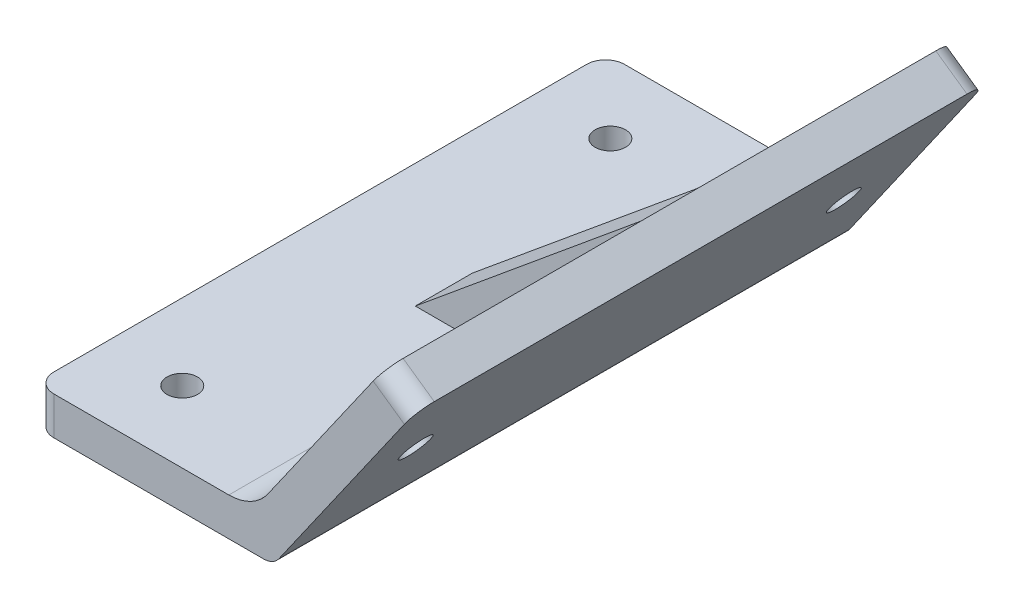
SolidWorks part; units mm, degrees
ref_plane "Front Plane" through (0, 0, 0) normal (0, 0, 1) x (1, 0, 0)
ref_plane "Top Plane" through (0, 0, 0) normal (0, 1, 0) x (1, 0, 0)
ref_plane "Right Plane" through (0, 0, 0) normal (1, 0, 0) x (0, 0, -1)
sketch "Sketch1" plane through (0, 0, 0) normal (0, 0, 1) x (1, 0, 0)
  line L0 (12.5411, -2) -> (27.4541, 19.298)
  line L1 (-12.5411, 2) -> (12.5411, 2)
  line L2 (-12.5411, 2) -> (-12.5411, -2)
  line L3 (-12.5411, -2) -> (12.5411, -2)
  line L4 (12.5411, 2) -> (12.5411, -2)
  line L5 (-12.5411, 2) -> (12.5411, -2) construction
  line L6 (-12.5411, -2) -> (12.5411, 2) construction
  line L7 (27.4541, 19.298) -> (24.1775, 21.5923)
  line L8 (24.1775, 21.5923) -> (10.4589, 2)
  point P0 (0, 0)
  dimension "D1" = 4
  dimension "D2" = 4
  dimension "D3" = 23
  dimension "D4" = 55
  dimension "D5" = 26
extrude "Boss-Extrude1" add sketch "Sketch1" against normal blind 30 and the other way blind 30 contours L7 L8 L1 L4 L0 | L4 L1 L2 L3 region at (18.9738, 10.6157, 0) region at (0, 0, 0)
sketch "Sketch2" plane through (0, 0, 0) normal (0, 0, 1) x (1, 0, 0)
  line L0 (24.1775, 21.5923) -> (0.4589, 2)
  line L1 (0.4589, 2) -> (10.4589, 2)
  line L6 (27.4541, 19.298) -> (24.1775, 21.5923)
  line L7 (24.1775, 21.5923) -> (10.4589, 2)
  line L8 (10.4589, 2) -> (-12.5411, 2)
  line L9 (-12.5411, 2) -> (-12.5411, -2)
  line L10 (-12.5411, -2) -> (12.5411, -2)
  line L11 (12.5411, -2) -> (27.4541, 19.298)
  line L12 (27.4541, 19.298) -> (24.1775, 21.5923)
  line L13 (24.1775, 21.5923) -> (10.4589, 2)
  line L14 (10.4589, 2) -> (-12.5411, 2)
  line L15 (-12.5411, 2) -> (-12.5411, -2)
  line L16 (-12.5411, -2) -> (12.5411, -2)
  line L17 (12.5411, -2) -> (27.4541, 19.298)
  dimension "D2" = 10
  dimension "D1" = 0
extrude "Boss-Extrude2" add sketch "Sketch2" along normal blind 3 and the other way blind 3 contours L13 L0 L1 region at (11.6984, 8.5308, 0)
sketch "Sketch3" plane through (9.3549, -6.5504, 0) normal (0.8192, -0.5736, 0) x (0, 0, -1)
  line L0 (-30, 18.555) -> (30, 18.555) construction
  line L1 (-30, 5.555) -> (-30, 31.555) construction
  line L2 (30, 5.555) -> (30, 31.555) construction
  line L3 (0, 31.555) -> (0, 5.555) construction
  line L4 (-30, 31.555) -> (30, 31.555) construction
  line L5 (-30, 5.555) -> (30, 5.555) construction
  circle A0 centre (-22.5, 18.555) radius 1.6
  circle A1 centre (22.5, 18.555) radius 1.6
  dimension "D1" = 3.2
  dimension "D2" = 45
  dimension "D3" = 22.5
extrude "Cut-Extrude1" cut sketch "Sketch3" against normal through all
sketch "Sketch4" plane through (0, 2, 0) normal (0, 1, 0) x (1, 0, 0)
  line L0 (-4.5411, 30) -> (-4.5411, -30) construction
  line L1 (-12.5411, 30) -> (10.4589, 30) construction
  line L2 (-12.5411, -30) -> (10.4589, -30) construction
  line L3 (0.4589, 3) -> (0.4589, -3) construction
  line L4 (-12.5411, 0) -> (0, 0) construction
  line L5 (-12.5411, -30) -> (-12.5411, 30) construction
  circle A0 centre (-4.5411, 22.5) radius 1.6
  circle A1 centre (-4.5411, -22.5) radius 1.6
  dimension "D2" = 3.2
  dimension "D1" = 5
  dimension "D3" = 45
  dimension "D4" = 22.5
extrude "Cut-Extrude2" cut sketch "Sketch4" against normal through all
fillet "Fillet1" radius 5 2 edges at (10.4589, 2, 16.5) (10.4589, 2, -16.5)
fillet "Fillet2" radius 2 3 edges at (25.8158, 20.4451, -30) (25.8158, 20.4451, 30) (12.5411, -2, 0)
fillet "Fillet3" radius 2 2 edges at (-12.5411, 0, -30) (-12.5411, 0, 30)
